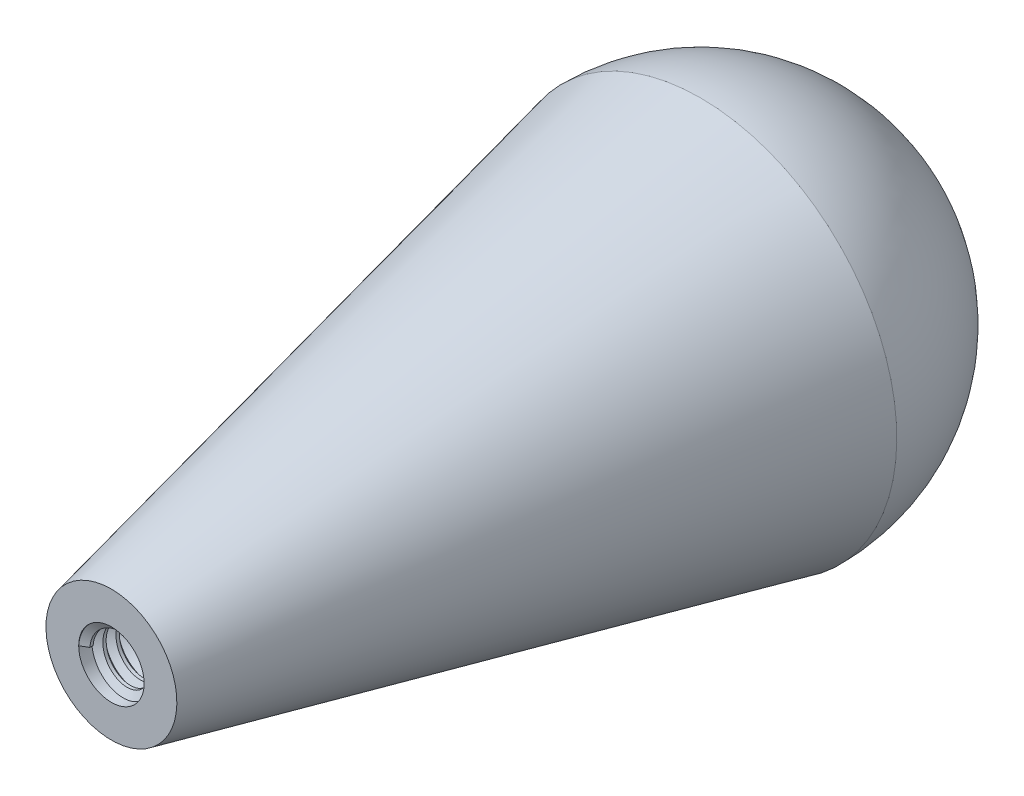
SolidWorks part; units mm, degrees
ref_plane "Front Plane" through (0, 0, 0) normal (0, 0, 1) x (1, 0, 0)
ref_plane "Top Plane" through (0, 0, 0) normal (0, 1, 0) x (1, 0, 0)
ref_plane "Right Plane" through (0, 0, 0) normal (1, 0, 0) x (0, 0, -1)
sketch "Sketch1" plane through (0, 0, 0) normal (1, 0, 0) x (0, 0, -1)
  line L0 (0, 0) -> (0, 5)
  line L1 (0, 0) -> (45, 0) construction
  line L2 (45, 0) -> (45, 15) construction
  line L3 (0, 5) -> (45, 15)
  line L4 (0, 0) -> (60, 0)
  arc A0 (45, 15) -> (60, 0) centre (45, 0) cw
revolve "Revolve1" add sketch "Sketch1" angle 360 about L4
hole_wizard "M6x1.0 Tapped Hole1" positions "Sketch7" profile "Sketch8" tap size "M6x1.0" standard "ANSI Metric"
sketch "Sketch7" plane through (0, 0, 0) normal (0, 0, 1) x (1, 0, 0)
  point P0 (0, 0)
sketch "Sketch8" plane through (0, 0, 0) normal (1, 0, 0) x (0, -1, 0)
  line L0 (0, 0) -> (0, 18.5022)
  line L1 (0, 18.5022) -> (2.5, 17)
  line L2 (2.5, 17) -> (2.5, 0)
  line L5 (2.5, 0) -> (0, 0)
  line L10 (0, 18.5022) -> (-2.5, 17) construction
  line L11 (0, -6.35) -> (0, 107.95) construction
  dimension "Tap Drill Dia." = 5
  dimension "Tap Drill Depth" = 17
  dimension "Drill Angle" = 118
cosmetic thread "Hole Thread1" parameters "D1"=12, "D2"=6
thread "Thread2" pitch 1 method extrude profile "Thread Profile2" start angle 0, offset 0, length 0, pitch 1, diameter 5
ref_plane "Plane6" through (-2.5, 0, 0) normal (0, -1, 0) x (-1, 0, 0)
sketch "Thread Profile2" plane through (-2.5, 0, 0) normal (0, -1, 0) x (-1, 0, 0)
  line L0 (0, 0) -> (0, 1) construction
  line L11 (0, 0) -> (0, 0.875)
  line L12 (0, 0.875) -> (-0.5413, 0.5625)
  line L13 (-0.5413, 0.5625) -> (-0.5413, 0.3125)
  line L15 (-0.5413, 0.3125) -> (0, 0)
  line L17 (-0.5413, 0.4375) -> (0, 0.4375) construction
  point P2 (0, 0)
  dimension "Pitch" = 1
  dimension "Profile_Angle" = 60
  dimension "Profile_Land" = 0.25
  dimension "Profile_Height" = 0.5413
